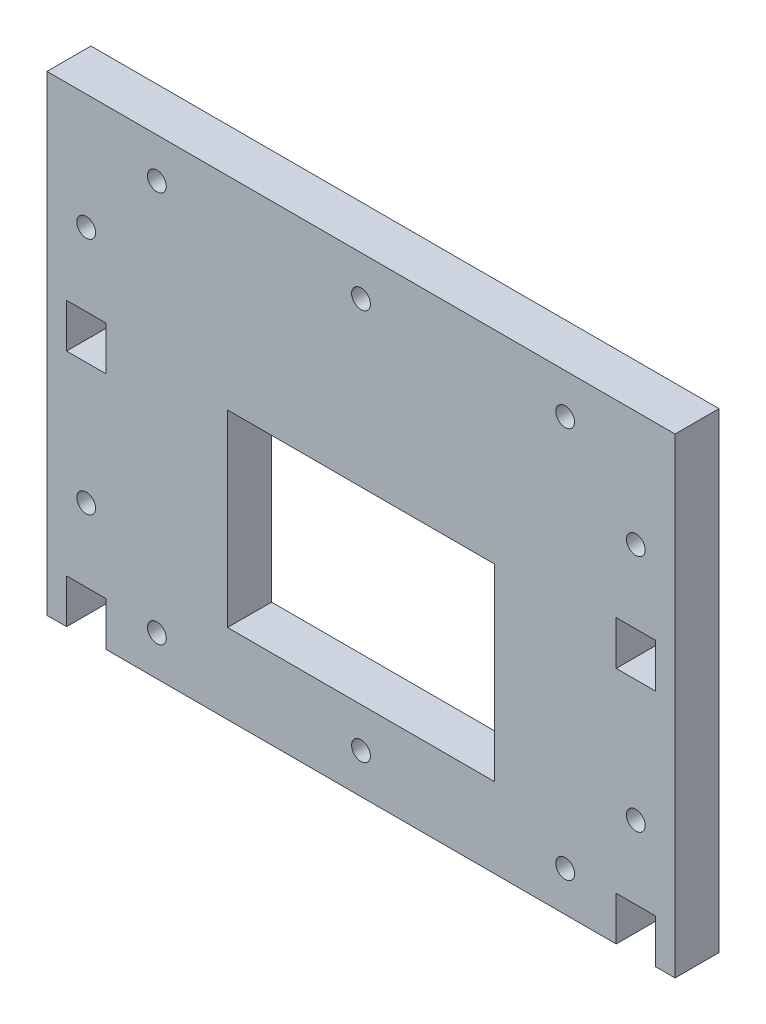
SolidWorks part; units mm, degrees
ref_plane "Front Plane" through (0, 0, 0) normal (0, 0, 1) x (1, 0, 0)
ref_plane "Top Plane" through (0, 0, 0) normal (0, 1, 0) x (1, 0, 0)
ref_plane "Right Plane" through (0, 0, 0) normal (1, 0, 0) x (0, 0, -1)
sketch "Sketch1" plane through (0, 0, 0) normal (0, 0, 1) x (1, 0, 0)
  line L1 (0, 0) -> (200, 0)
  line L2 (0, 0) -> (0, 150)
  line L3 (0, 150) -> (200, 150)
  line L4 (200, 0) -> (200, 150)
  dimension "D1" = 200
  dimension "D2" = 150
extrude "Boss-Extrude1" add sketch "Sketch1" along normal blind 14
sketch "Sketch2" plane through (0, 0, 0) normal (0, 0, -1) x (-1, 0, 0)
  line L4 (-18.75, 0) -> (-6.25, 0) construction
  line L5 (-6.25, 0) -> (-6.25, 14) construction
  line L6 (-6.25, 14) -> (-18.75, 14) construction
  line L7 (-18.75, 14) -> (-18.75, 0) construction
  line L12 (-193.75, 0) -> (-181.25, 0) construction
  line L13 (-181.25, 0) -> (-181.25, 14) construction
  line L14 (-181.25, 14) -> (-193.75, 14) construction
  line L15 (-193.75, 14) -> (-193.75, 0) construction
  line L20 (-18.75, 0) -> (-6.25, 0)
  line L21 (-6.25, 0) -> (-6.25, 14)
  line L22 (-6.25, 14) -> (-18.75, 14)
  line L23 (-18.75, 14) -> (-18.75, 0)
  line L28 (-193.75, 0) -> (-181.25, 0)
  line L29 (-181.25, 0) -> (-181.25, 14)
  line L30 (-181.25, 14) -> (-193.75, 14)
  line L31 (-193.75, 14) -> (-193.75, 0)
  line L32 (-18.75, 76) -> (-6.25, 76)
  line L33 (-6.25, 76) -> (-6.25, 90)
  line L34 (-6.25, 90) -> (-18.75, 90)
  line L35 (-18.75, 90) -> (-18.75, 76)
  line L36 (-193.75, 76) -> (-181.25, 76)
  line L37 (-181.25, 76) -> (-181.25, 90)
  line L38 (-181.25, 90) -> (-193.75, 90)
  line L39 (-193.75, 90) -> (-193.75, 76)
  line L40 (0, 0) -> (-200, 0) construction
  dimension "D1" = 76
extrude "Cut-Extrude1" cut sketch "Sketch2" against normal up to surface (14 mm away) up to face at (100, 75, 14)
sketch "Sketch3" plane through (0, 0, 14) normal (0, 0, 1) x (1, 0, 0)
  line L0 (200, 150) -> (0, 150) construction
  line L1 (0, 75) -> (200, 75) construction
  line L2 (0, 150) -> (0, 0) construction
  line L3 (200, 0) -> (200, 150) construction
  point P0 (12.5, 113.2657)
  point P1 (187.5, 113.2657)
  point P3 (100, 137.3)
  point P5 (165, 137.3)
  point P6 (35, 137.3)
  point P7 (12.5, 37.2657)
  point P9 (187.5, 37.2657)
  point P20 (35, 12.7)
  point P21 (165, 12.7)
  point P22 (100, 12.7)
  point P24 (100, 75)
  dimension "D1" = 12.7
  dimension "D2" = 65
  dimension "D3" = 65
hole_wizard "Ø6.0 (6) Diameter Hole1" positions "Sketch4" profile "Sketch5" hole size "Ø6.0" standard "ANSI Metric" end condition through all
sketch "Sketch4" plane through (0, 0, 14) normal (0, 0, 1) x (1, 0, 0)
  point P0 (12.5, 113.2657)
  point P3 (187.5, 113.2657)
  point P6 (187.5, 37.2657)
  point P9 (12.5, 37.2657)
  point P14 (35, 137.3)
  point P17 (100, 137.3)
  point P20 (165, 137.3)
  point P23 (165, 12.7)
  point P26 (100, 12.7)
  point P29 (35, 12.7)
sketch "Sketch5" plane through (12.5, 113.2657, 14) normal (1, 0, 0) x (0, -1, 0)
  line L0 (0, 0) -> (0, 14)
  line L1 (0, 14) -> (3, 14)
  line L2 (3, 14) -> (3, 0)
  line L5 (3, 0) -> (0, 0)
  line L11 (0, -6.35) -> (0, 107.95) construction
  dimension "Thru Hole Dia." = 6
  dimension "Thru Hole Depth" = 14
sketch "Sketch6" plane through (0, 0, 14) normal (0, 0, 1) x (1, 0, 0)
  line L1 (57.5, 25.4) -> (142.5, 25.4)
  line L2 (57.5, 25.4) -> (57.5, 85.4)
  line L3 (57.5, 85.4) -> (142.5, 85.4)
  line L4 (142.5, 25.4) -> (142.5, 85.4)
  line L5 (57.5, 25.4) -> (142.5, 85.4) construction
  line L6 (57.5, 85.4) -> (142.5, 25.4) construction
  line L7 (0, 150) -> (0, 0) construction
  line L8 (18.75, 0) -> (181.25, 0) construction
  point P0 (100, 55.4)
  dimension "D1" = 60
  dimension "D2" = 85
  dimension "D3" = 25.4
  dimension "D4" = 100
extrude "Cut-Extrude2" cut sketch "Sketch6" against normal through all
